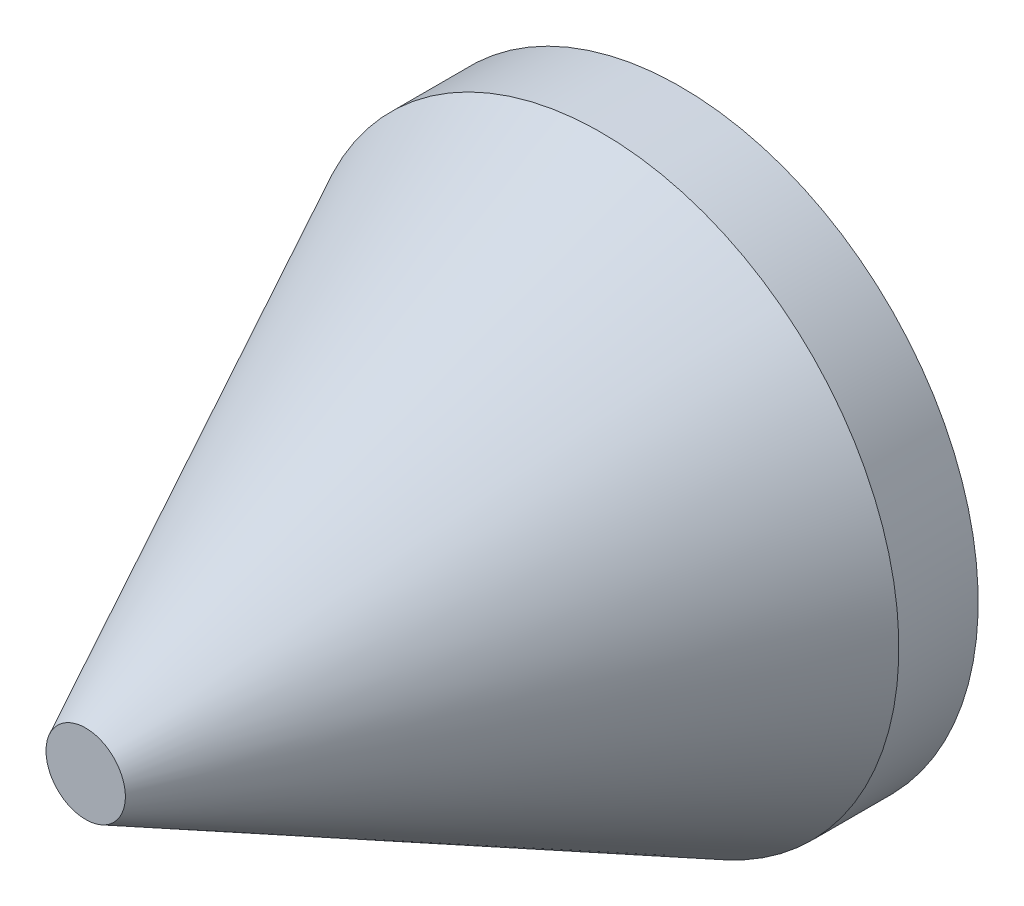
SolidWorks part; units mm, degrees
ref_plane "Front Plane" through (0, 0, 0) normal (0, 0, 1) x (1, 0, 0)
ref_plane "Top Plane" through (0, 0, 0) normal (0, 1, 0) x (1, 0, 0)
ref_plane "Right Plane" through (0, 0, 0) normal (1, 0, 0) x (0, 0, -1)
sketch "Sketch1" plane through (0, 0, 0) normal (0, 1, 0) x (1, 0, 0)
  line L0 (0, 14.5439) -> (0, -58.0895) construction
  line L2 (75, 0) -> (0, 0)
  line L3 (0, 0) -> (0, -150)
  line L4 (75, 0) -> (75, -20)
  line L6 (0, -150) -> (10, -150)
  line L7 (10, -150) -> (75, -20)
  dimension "D1" = 150
  dimension "D2" = 75
  dimension "D3" = 20
  dimension "D4" = 10
revolve "Revolve1" add sketch "Sketch1" angle 360 about L0
ref_axis "Axis1" through (0, 0, 157.5) along (0, 0, -1)
equation "\"end_effector_diameter\"=150"
equation "\"D2@Sketch1\"=\"end_effector_diameter\"/2"
equation "\"end_effector_length\"=150"
equation "\"D1@Sketch1\"=\"end_effector_length\""
equation "\"base_link_length\"=150"
equation "\"link1_diameter\"=150"
equation "\"link1_length\"=150"
equation "\"link2_diameter\"=150"
equation "\"link2_length\"=300"
equation "\"link3_diameter\"=150"
equation "\"link3_length\"=150"
equation "\"link4_diameter\"=150"
equation "\"link4_length\"=150"
equation "\"link5_diameter\"=150"
equation "\"link5_length\"=200"
equation "\"base_link_diameterA\"=200"
equation "\"base_link_diameterB\"=150"
equation "\"base_link_lengthA\"=50"
